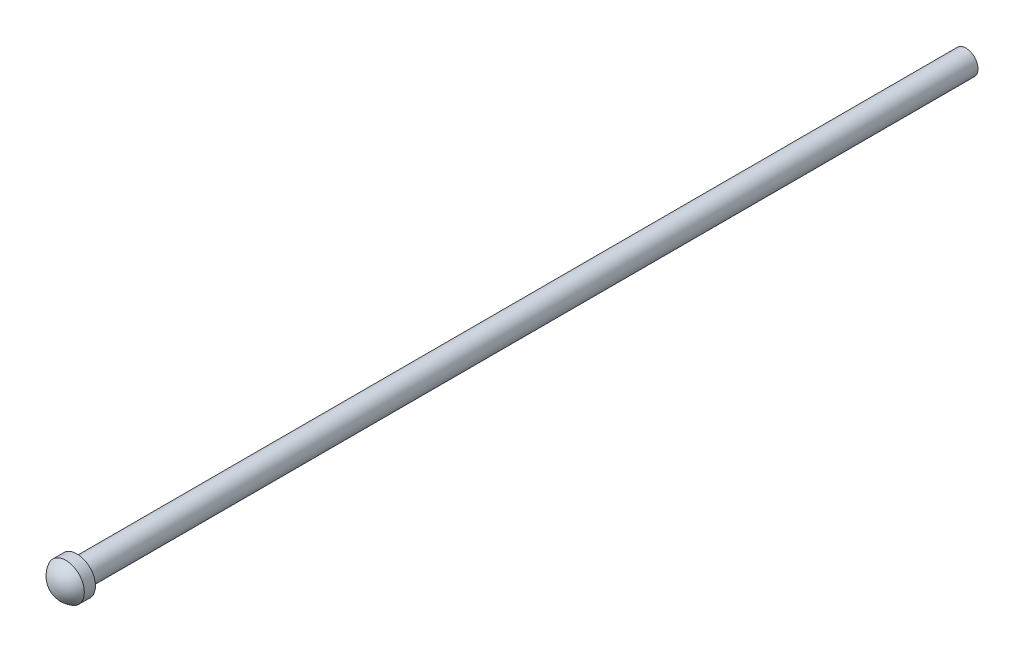
SolidWorks part; units mm, degrees
ref_plane "Front Plane" through (0, 0, 0) normal (0, 0, 1) x (1, 0, 0)
ref_plane "Top Plane" through (0, 0, 0) normal (0, 1, 0) x (1, 0, 0)
ref_plane "Right Plane" through (0, 0, 0) normal (1, 0, 0) x (0, 0, -1)
sketch "Эскиз1" plane through (0, 0, 0) normal (0, 0, 1) x (1, 0, 0)
  circle A2 centre (5, 60) radius 3.25
  circle A3 centre (5, 60) radius 3.25
  dimension "D1" = 0.25
sketch "Эскиз2" plane through (0, 0, -120) normal (1, 0, 0) x (0, 0, -1)
  line L0 (-120, 0) -> (120, 0) construction
  line L1 (-120, 0) -> (120, 0)
sweep "По траектории1" add profiles "Эскиз1" path "Эскиз2"
sketch "Эскиз3" plane through (0, 0, 0) normal (0, 0, 1) x (1, 0, 0)
  circle A0 centre (5, 60) radius 5
  arc A1 (5, 55) -> (0, 60) centre (5, 60) ccw construction
extrude "Бобышка-Вытянуть1" add sketch "Эскиз3" along normal blind 3
dome "Купол1" faces to dome 1 distance 3 reverse direction no elliptical dome no face at (10, 60, 3) parameters "D1"=3
